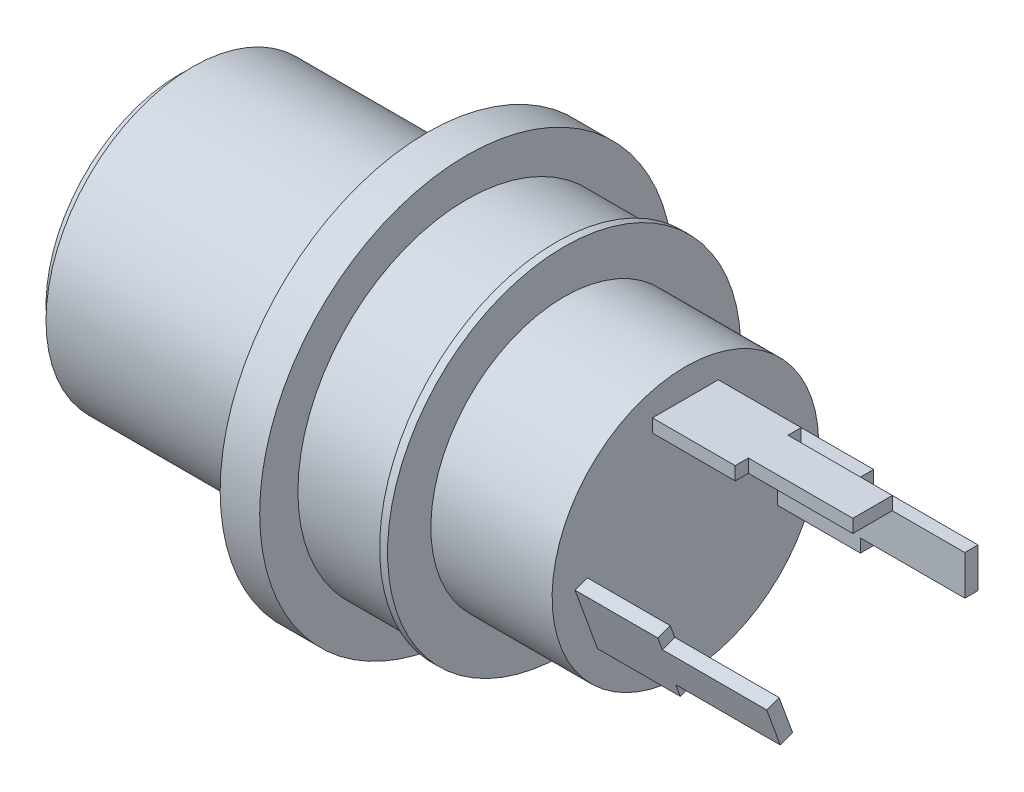
SolidWorks part; units mm, degrees
material "Nickel silver 65-12, UNS C75700"
ref_plane "Front Plane" through (0, 0, 0) normal (0, 0, 1) x (1, 0, 0)
ref_plane "Top Plane" through (0, 0, 0) normal (0, 1, 0) x (1, 0, 0)
ref_plane "Right Plane" through (0, 0, 0) normal (1, 0, 0) x (0, 0, -1)
sketch "Sketch1" plane through (0, 0, 0) normal (0, 0, 1) x (1, 0, 0)
  line L0 (0, 0) -> (-19.2, 0) construction
  line L1 (-19.2, 0) -> (-19.2, 5.0562)
  line L2 (-19.2, 5.0562) -> (-18.7, 5.0562)
  line L3 (-18.7, 5.0562) -> (-18.7, 5.5562)
  line L4 (-18.7, 5.5562) -> (-9.8, 5.5562)
  line L5 (-9.8, 5.5562) -> (-9.8, 7.85)
  line L6 (-9.8, 7.85) -> (-8.3, 7.85)
  line L7 (-8.3, 7.85) -> (-8.3, 6.4)
  line L8 (-8.3, 6.4) -> (-4.9, 6.4)
  line L9 (-4.9, 6.4) -> (-4.9, 6.7)
  line L10 (-4.9, 6.7) -> (-4.6, 6.7)
  line L11 (-4.6, 6.7) -> (-4.6, 5.0562)
  line L12 (-4.6, 5.0562) -> (0, 5.0562)
  line L13 (0, 5.0562) -> (0, 0)
  line L14 (0, 0) -> (-19.2, 0)
  dimension "D1" = 11.1125
  dimension "D2" = 9.4
  dimension "D3" = 15.7
  dimension "D4" = 13.4
  dimension "D5" = 0.3
  dimension "D6" = 19.2
  dimension "D7" = 0.5
  dimension "D8" = 1.5
  dimension "D9" = 5.2
revolve "Revolve1" add sketch "Sketch1" angle 360 about L0
sketch "Sketch2" plane through (-19.2, 0, 0) normal (-1, 0, 0) x (0, 0, 1)
  circle A0 centre (0, 0) radius 3.5563
  circle A1 centre (0, 0) radius 5.0563 construction
  dimension "D1" = 1.5
extrude "Cut-Extrude1" cut sketch "Sketch2" against normal offset from surface (7.9 mm away) 1.5 up to face at (-9.8, 5.5562, 0)
sketch "Sketch3" plane through (0, 0, 0) normal (1, 0, 0) x (0, 0, -1)
  line L0 (-1.25, 3.75) -> (1.25, 3.75)
  line L1 (3.75, 1.25) -> (3.75, -1.25)
  line L2 (-3.9514, -0.108) -> (-3.0963, -2.4572)
  line L3 (0, 3.75) -> (0, 0) construction
  line L4 (0, 0) -> (3.75, 0) construction
  line L5 (0, 0) -> (-3.5238, -1.2826) construction
  dimension "D1" = 2.5
  dimension "D2" = 20
  dimension "D3" = 3.75
extrude "Extrude-Thin1" add sketch "Sketch3" along normal offset from surface (7.1 mm away) 26.3 thin up to face at (-19.2, -3.5563, 0) thin type mid plane wall 0.5
sketch "Sketch4" plane through (7.1, 0, 0) normal (1, 0, 0) x (0, 0, -1)
  line L0 (1.25, 3.5) -> (-1.25, 3.5) construction
  line L1 (-1.25, 4) -> (-0.75, 4)
  line L2 (-1.25, 4) -> (-1.25, 3.5)
  line L3 (-1.25, 3.5) -> (-0.75, 3.5)
  line L4 (-0.75, 4) -> (-0.75, 3.5)
  line L5 (1.25, 4) -> (-1.25, 4) construction
  line L6 (1.25, 3.5) -> (0.75, 3.5)
  line L7 (1.25, 3.5) -> (1.25, 4)
  line L8 (1.25, 4) -> (0.75, 4)
  line L9 (0.75, 3.5) -> (0.75, 4)
  line L10 (4, 1.25) -> (4, -1.25) construction
  line L11 (3.5, 1.25) -> (4, 1.25)
  line L12 (3.5, 1.25) -> (3.5, 0.75)
  line L13 (3.5, 0.75) -> (4, 0.75)
  line L14 (4, 1.25) -> (4, 0.75)
  line L15 (4, -1.25) -> (4, 1.25) construction
  line L16 (3.5, -1.25) -> (4, -1.25)
  line L17 (3.5, -1.25) -> (3.5, -0.75)
  line L18 (3.5, -0.75) -> (4, -0.75)
  line L19 (4, -1.25) -> (4, -0.75)
  line L20 (-3.3312, -2.5427) -> (-2.8614, -2.3717)
  line L21 (-3.3312, -2.5427) -> (-3.5023, -2.0729)
  line L22 (-2.8614, -2.3717) -> (-3.0324, -1.9018)
  line L23 (-3.5023, -2.0729) -> (-3.0324, -1.9018)
  line L24 (-3.7164, -0.0225) -> (-4.1863, -0.1935)
  line L25 (-3.7164, -0.0225) -> (-3.5454, -0.4923)
  line L26 (-4.1863, -0.1935) -> (-4.0153, -0.6633)
  line L27 (-3.5454, -0.4923) -> (-4.0153, -0.6633)
extrude "Cut-Extrude3" cut sketch "Sketch4" against normal blind 3.96
